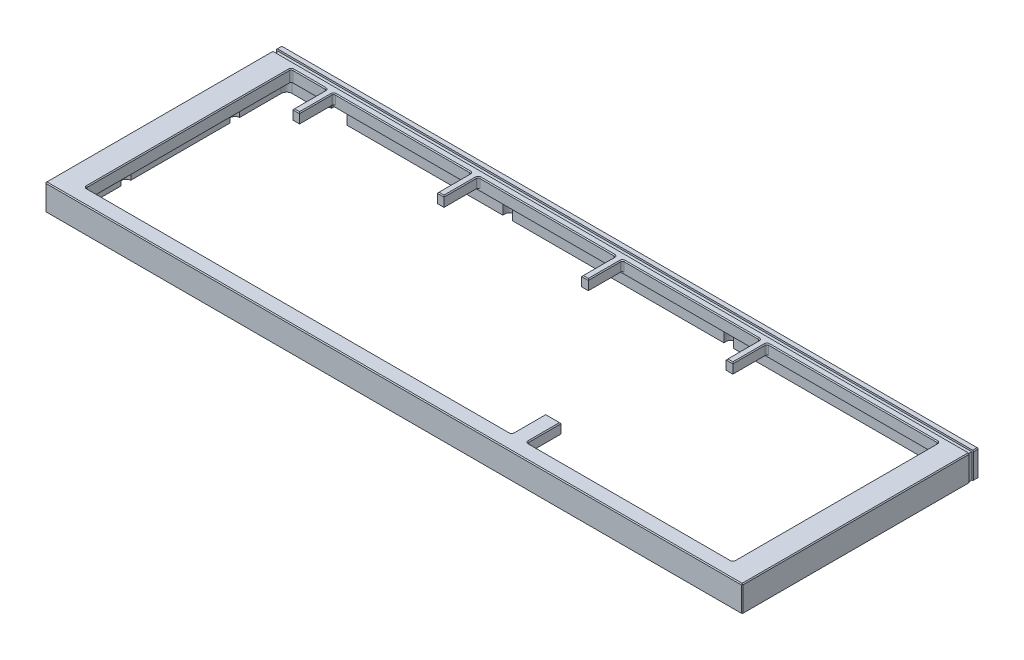
SolidWorks part; units mm, degrees
material "6061-T6 (SS)"
ref_plane "Front Plane" through (0, 0, 0) normal (0, 0, 1) x (1, 0, 0)
ref_plane "Top Plane" through (0, 0, 0) normal (0, 1, 0) x (1, 0, 0)
ref_plane "Right Plane" through (0, 0, 0) normal (1, 0, 0) x (0, 0, -1)
sketch "Sketch1" plane through (0, 0, 0) normal (0, 1, 0) x (1, 0, 0)
  line L1 (0, 0) -> (390.74, 0)
  line L2 (0, 0) -> (0, 132.7)
  line L3 (0, 132.7) -> (390.74, 132.7)
  line L4 (390.74, 0) -> (390.74, 132.7)
  line L5 (13.92, 124) -> (376.82, 124)
  line L6 (13.92, 124) -> (13.92, 8.7)
  line L7 (13.92, 8.7) -> (376.82, 8.7)
  line L8 (376.82, 124) -> (376.82, 8.7)
  point P9 (195.37, 124)
  point P10 (195.37, 132.7)
  point P11 (13.92, 66.35)
  point P12 (0, 66.35)
  dimension "D1" = 362.9
  dimension "D2" = 115.3
  dimension "D3" = 8.7
  dimension "D4" = 13.92
extrude "Main Body" add sketch "Sketch1" along normal blind 14.8
sketch "Sketch2" plane through (0, 0, 0) normal (0, -1, 0) x (1, 0, 0)
  line L0 (390.74, -132.7) -> (0, -132.7) construction
  line L1 (388.74, -130.7) -> (2, -130.7)
  line L2 (388.74, -130.7) -> (388.74, -2)
  line L3 (388.74, -2) -> (2, -2)
  line L4 (2, -130.7) -> (2, -2)
  line L5 (390.74, 0) -> (390.74, -132.7) construction
  point P4 (195.37, -130.7)
  point P7 (195.37, -132.7)
  point P8 (388.74, -66.35)
  point P11 (390.74, -66.35)
  dimension "D1" = 2
  dimension "D2" = 2
extrude "Alignment Guide" cut sketch "Sketch2" against normal blind 1 contours L2 L1 L4 L3
sketch "Sketch3" plane through (0, 14.8, 0) normal (0, 1, 0) x (1, 0, 0)
  line L0 (13.92, 8.7) -> (376.82, 8.7) construction
  line L1 (252.82, 27.8) -> (261.52, 27.8)
  line L2 (252.82, 27.8) -> (252.82, 8.7)
  line L3 (252.82, 8.7) -> (261.52, 8.7)
  line L4 (261.52, 27.8) -> (261.52, 8.7)
  line L5 (376.82, 8.7) -> (376.82, 124) construction
  line L6 (376.82, 124) -> (13.92, 124) construction
  line L7 (33.92, 124) -> (37.72, 124)
  line L8 (33.92, 124) -> (33.92, 104.9)
  line L9 (33.92, 104.9) -> (37.72, 104.9)
  line L10 (37.72, 124) -> (37.72, 104.9)
  line L11 (13.92, 124) -> (13.92, 8.7) construction
  line L12 (114.92, 124) -> (118.72, 124)
  line L13 (114.92, 124) -> (114.92, 104.9)
  line L14 (114.92, 104.9) -> (118.72, 104.9)
  line L15 (118.72, 124) -> (118.72, 104.9)
  line L16 (195.82, 124) -> (199.62, 124)
  line L17 (195.82, 124) -> (195.82, 104.9)
  line L18 (195.82, 104.9) -> (199.62, 104.9)
  line L19 (199.62, 124) -> (199.62, 104.9)
  line L20 (276.82, 124) -> (280.62, 124)
  line L21 (276.82, 124) -> (276.82, 104.9)
  line L22 (276.82, 104.9) -> (280.62, 104.9)
  line L23 (280.62, 124) -> (280.62, 104.9)
  point P8 (257.17, 8.7)
  dimension "D1" = 115.3
  dimension "D2" = 124
  dimension "D3" = 19.1
  dimension "D4" = 3.8
  dimension "D5" = 19.1
  dimension "D6" = 77.2
  dimension "D7" = 77.1
  dimension "D8" = 77.2
  dimension "D9" = 20
extrude "Blockers" add sketch "Sketch3" against normal blind 5.5
fillet "Fillet5" radius 1 14 edges at (280.62, 12.05, -124) (276.82, 12.05, -124) (195.82, 12.05, -124) (199.62, 12.05, -124) (118.72, 12.05, -124) (114.92, 12.05, -124) (33.92, 12.05, -124) (37.72, 12.05, -124) (13.92, 7.9, -124) (13.92, 7.9, -8.7) (252.82, 12.05, -8.7) (261.52, 12.05, -8.7) (376.82, 7.9, -8.7) (376.82, 7.9, -124)
sketch "Sketch4" plane through (0, 1, 0) normal (0, -1, 0) x (1, 0, 0)
  line L0 (0, 0) -> (390.74, 0) construction
  line L1 (381.27, -125.9) -> (9.47, -125.9)
  line L2 (381.27, -125.9) -> (381.27, -6.8)
  line L3 (381.27, -6.8) -> (9.47, -6.8)
  line L4 (9.47, -125.9) -> (9.47, -6.8)
  line L5 (390.74, 0) -> (390.74, -132.7) construction
  point P4 (195.37, -6.8)
  point P7 (195.37, 0)
  point P8 (381.27, -66.35)
  point P11 (390.74, -66.35)
  dimension "D1" = 119.1
  dimension "D2" = 371.8
extrude "PCB Cutout" cut sketch "Sketch4" against normal offset from surface (7.3 mm away) 6.5 up to face at (195.37, 14.8, -66.35)
fillet "Fillet4" radius 3 8 edges at (9.47, 4.65, -6.8) (9.47, 4.65, -125.9) (381.27, 4.65, -125.9) (381.27, 4.65, -6.8) (2, 0.5, -130.7) (2, 0.5, -2) (388.74, 0.5, -2) (388.74, 0.5, -130.7)
sketch "Sketch6" plane through (0, 1, 0) normal (0, -1, 0) x (1, 0, 0)
  line L0 (381.27, -9.8) -> (381.27, -122.9) construction
  line L1 (254.59, -127.1) -> (260.09, -127.1)
  line L2 (254.59, -127.1) -> (254.59, -125.9)
  line L3 (254.59, -125.9) -> (260.09, -125.9)
  line L4 (260.09, -127.1) -> (260.09, -125.9)
  line L5 (12.47, -125.9) -> (378.27, -125.9) construction
  line L11 (378.27, -6.8) -> (12.47, -6.8) construction
  line L16 (260.09, -6.8) -> (254.59, -6.8)
  line L17 (260.09, -6.8) -> (260.09, -4.8)
  line L18 (260.09, -4.8) -> (254.59, -4.8)
  line L19 (254.59, -6.8) -> (254.59, -4.8)
  line L21 (0, 0) -> (390.74, 0) construction
  line L24 (390.74, -66.35) -> (195.37, -66.35) construction
  line L25 (390.74, 0) -> (390.74, -132.7) construction
  line L26 (328.6755, -66.35) -> (328.6755, -130.7) construction
  line L27 (385.74, -130.7) -> (5, -130.7) construction
  line L28 (328.6755, -66.35) -> (328.6755, -8.7) construction
  line L29 (375.82, -8.7) -> (14.92, -8.7) construction
  line L55 (390.74, -132.7) -> (0, -132.7) construction
  line L56 (195.37, -132.7) -> (195.37, 0) construction
  line L57 (136.15, -6.8) -> (136.15, -4.8)
  line L58 (130.65, -4.8) -> (136.15, -4.8)
  line L59 (130.65, -6.8) -> (130.65, -4.8)
  line L60 (130.65, -6.8) -> (136.15, -6.8)
  line L61 (130.65, -127.1) -> (130.65, -125.9)
  line L62 (136.15, -125.9) -> (130.65, -125.9)
  line L63 (136.15, -127.1) -> (136.15, -125.9)
  line L64 (136.15, -127.1) -> (130.65, -127.1)
  circle A0 centre (381.07, -96.85) radius 2.75
  circle A1 centre (381.07, -35.85) radius 2.75
  circle A2 centre (257.34, -4.8) radius 2.75
  circle A3 centre (257.34, -127.1) radius 2.75
  circle A8 centre (133.4, -4.8) radius 2.75
  circle A9 centre (9.67, -35.85) radius 2.75
  circle A10 centre (9.67, -96.85) radius 2.75
  circle A11 centre (133.4, -127.1) radius 2.75
  point P25 (195.37, -66.35)
  point P32 (257.34, -125.9)
  point P33 (257.34, -6.8)
  line M17 (12.47, -6.8) -> (378.27, -6.8)
  line M18 (381.27, -9.8) -> (381.27, -122.9)
  line M19 (378.27, -125.9) -> (12.47, -125.9)
  line M20 (9.47, -122.9) -> (9.47, -9.8)
  dimension "D4" = 5.5
  dimension "D5" = 133.4
  dimension "D1" = 30.5
  dimension "D2" = 4.8
  dimension "D3" = 30.5
  dimension "D6" = 0.2
  dimension "D7" = 5.6
extrude "PlateTabs" cut sketch "Sketch6" against normal up to surface (7.3 mm away) contours A0 M18 | A1 M18 | A2 L19 M17 | L16 A2 L18 | A2 L17 M17 | L18 A2 | L1 A3 | L1 A3 L3 | A3 L2 M19 | A11 L64 | A11 L64 L62 | A10 M20 | A9 M20 | A8 L58 | A8 L60 L58 | A3 L4 M19 | A8 L59 M17 | L57 A8 M17 | A11 L63 M19 | L61 A11 M19 | A11 | L59 L58 L57 L60 | A3 region at (257.34, 1, -126.5102) region at (136.0681, 1, -126.1969) region at (257.34, 1, -128.2671) region at (254.6719, 1, -126.1969) region at (260.0081, 1, -126.1969) region at (133.4, 1, -126.5102) region at (133.4, 1, -128.2671) region at (130.7319, 1, -126.1969) region at (135.9001, 1, -6.317) region at (259.8401, 1, -6.317) region at (257.34, 1, -5.7445) region at (257.34, 1, -3.6329) region at (254.8399, 1, -6.317) region at (133.4, 1, -5.7445) region at (133.4, 1, -3.6329) region at (130.8999, 1, -6.317) region at (382.3459, 1, -96.85) region at (382.3459, 1, -35.85) region at (8.3941, 1, -96.85) region at (8.3941, 1, -35.85) up to face at (195.37, 8.3, -66.35)
sketch "Sketch9" plane through (0, 0, -132.7) normal (0, 0, -1) x (-1, 0, 0)
  line L1 (-41.8, 0) -> (-29.8, 0)
  line L2 (-41.8, 0) -> (-41.8, 3.2)
  line L3 (-41.8, 3.2) -> (-29.8, 3.2)
  line L4 (-29.8, 0) -> (-29.8, 3.2)
  line L5 (-390.74, 0) -> (0, 0) construction
  line L7 (0, 14.8) -> (0, 0) construction
  point P6 (-35.8, 3.2)
  dimension "D1" = 3.2
  dimension "D3" = 12
  dimension "D4" = 35.8
extrude "USB Cutout" cut sketch "Sketch9" against normal up to surface (8.7 mm away) up to face at (164.89, 11.95, -124)
sketch "Sketch11" plane through (0, 0, -125.9) normal (0, 0, 1) x (1, 0, 0)
  line L0 (130.65, 8.3) -> (12.47, 8.3) construction
  line L1 (43.3, 1) -> (28.3, 1)
  line L2 (43.3, 1) -> (43.3, 8.3)
  line L3 (43.3, 8.3) -> (28.3, 8.3)
  line L4 (28.3, 1) -> (28.3, 8.3)
  line L7 (12.47, 1) -> (29.8, 1) construction
  line L8 (29.8, 3.2) -> (41.8, 3.2) construction
  point P8 (35.8, 1)
  point P12 (0, 0)
  point P13 (0, 0)
  point P14 (0, 0)
  point P15 (0, 0)
  point P18 (35.8, 3.2)
  dimension "D1" = 15
extrude "PCB Clearance" cut sketch "Sketch11" against normal blind 3.9
fillet "Fillet7" radius 2.5 2 edges at (28.3, 4.65, -129.8) (43.3, 4.65, -129.8)
sketch "Sketch12" plane through (0, 8.3, 0) normal (0, -1, 0) x (1, 0, 0)
  line L0 (195.37, -132.7) -> (195.37, 0) construction
  line L2 (14.92, -124) -> (375.82, -124) construction
  line L3 (0, 0) -> (390.74, 0) construction
  line L4 (390.74, 0) -> (390.74, -132.7) construction
  line L5 (390.74, -132.7) -> (41.8, -132.7) construction
  line L8 (376.82, -123) -> (376.82, -9.7) construction
  line L9 (375.82, -8.7) -> (14.92, -8.7) construction
  arc A0 (381.27, -38.5927) -> (381.27, -33.1073) centre (381.07, -35.85) ccw construction
  arc A1 (381.27, -99.5927) -> (381.27, -94.1073) centre (381.07, -96.85) ccw construction
  point P0 (257.34, -127.1)
  point P1 (381.42, -96.85)
  point P2 (381.42, -35.85)
  point P3 (257.34, -4.8)
  point P7 (195.37, -131.4428)
  point P8 (133.4, -4.8)
  point P10 (9.32, -35.85)
  point P12 (0, 0)
  point P14 (9.32, -96.85)
  point P16 (133.4, -127.1)
  point P34 (383.82, -35.85)
  point P39 (383.82, -96.85)
  dimension "D1" = 3.1
  dimension "D2" = 3.9
  dimension "D3" = 4.6
  dimension "D4" = 133.4
sketch "Sketch14" plane through (0, 1, 0) normal (0, -1, 0) x (1, 0, 0)
  line L0 (195.37, -132.7) -> (195.37, 0) construction
  line L2 (0, 0) -> (390.74, 0) construction
  line L3 (390.74, -132.7) -> (41.8, -132.7) construction
  line L5 (195.37, -66.35) -> (390.74, -66.35) construction
  line L6 (390.74, 0) -> (390.74, -132.7) construction
  line L7 (388.74, -127.7) -> (388.74, -5) construction
  line L8 (385.74, -130.7) -> (41.8, -130.7) construction
  line L9 (385.74, -2) -> (5, -2) construction
  point P2 (0, 0)
  point P8 (385.04, -111.35)
  point P9 (385.04, -66.35)
  point P10 (385.04, -21.35)
  point P11 (280.74, -4.4)
  point P20 (280.74, -128.3)
  point P22 (110, -4.4)
  point P28 (110, -128.3)
  point P29 (5.7, -21.35)
  point P30 (5.7, -66.35)
  point P31 (5.7, -111.35)
  dimension "D1" = 2.4
  dimension "D2" = 2.4
  dimension "D3" = 110
  dimension "D4" = 45
  dimension "D5" = 45
  dimension "D6" = 3.7
chamfer "Chamfer1" distance 0.5 42 edges at (14.2129, 14.8, -8.9929) (133.37, 14.8, -8.7) (252.5271, 14.8, -8.9929) (252.82, 14.8, -18.75) (257.17, 14.8, -27.8) (261.52, 14.8, -18.75) (261.8129, 14.8, -8.9929) (319.17, 14.8, -8.7) (376.5271, 14.8, -8.9929) (376.82, 14.8, -66.35) (376.5271, 14.8, -123.7071) (328.72, 14.8, -124) (280.9129, 14.8, -123.7071) (280.62, 14.8, -113.95) (278.72, 14.8, -104.9) (276.82, 14.8, -113.95) (276.5271, 14.8, -123.7071) (238.22, 14.8, -124) (199.9129, 14.8, -123.7071) (199.62, 14.8, -113.95) (197.72, 14.8, -104.9) (195.82, 14.8, -113.95) (195.5271, 14.8, -123.7071) (157.27, 14.8, -124) (119.0129, 14.8, -123.7071) (118.72, 14.8, -113.95) (116.82, 14.8, -104.9) (114.92, 14.8, -113.95) (114.6271, 14.8, -123.7071) (76.32, 14.8, -124) (38.0129, 14.8, -123.7071) (37.72, 14.8, -113.95) (35.82, 14.8, -104.9) (33.92, 14.8, -113.95) (33.6271, 14.8, -123.7071) (23.92, 14.8, -124) (14.2129, 14.8, -123.7071) (13.92, 14.8, -66.35) (195.37, 14.8, -132.7) (390.74, 14.8, -66.35) (195.37, 14.8, 0) (0, 14.8, -66.35)
chamfer "Chamfer2" distance 0.5 9 edges at (0, 7.15, -132.7) (216.27, 0, -132.7) (14.9, 0, -132.7) (390.74, 7.15, -132.7) (390.74, 0, -66.35) (390.74, 7.15, 0) (0, 7.15, 0) (195.37, 0, 0) (0, 0, -66.35)
sketch "Sketch27" plane through (0, 14.8, 0) normal (0, 1, 0) x (1, 0, 0)
  line L0 (0, 0.5) -> (0, 132.2) construction
  line L1 (0, 129.7) -> (390.74, 129.7)
  line L2 (0, 129.7) -> (0, 127.2)
  line L3 (0, 127.2) -> (390.74, 127.2)
  line L4 (390.74, 129.7) -> (390.74, 127.2)
  line L5 (390.74, 132.2) -> (390.74, 0.5) construction
  line L8 (0.5, 132.7) -> (390.24, 132.7) construction
  dimension "D1" = 2.5
  dimension "D2" = 3
extrude "Cut-Extrude11" cut sketch "Sketch27" against normal blind 1
sketch "Sketch28" plane through (0, 13.8, 0) normal (0, 1, 0) x (1, 0, 0)
  line L1 (0, 129.7) -> (1, 129.7)
  line L2 (0, 129.7) -> (0, 127.2)
  line L3 (0, 127.2) -> (1, 127.2)
  line L4 (1, 129.7) -> (1, 127.2)
  line L5 (389.74, 129.7) -> (390.74, 129.7)
  line L6 (389.74, 129.7) -> (389.74, 127.2)
  line L7 (389.74, 127.2) -> (390.74, 127.2)
  line L8 (390.74, 129.7) -> (390.74, 127.2)
  line L9 (390.74, 129.7) -> (0, 129.7) construction
  line L10 (0, 127.2) -> (390.74, 127.2) construction
  dimension "D1" = 1
  dimension "D2" = 1
extrude "Cut-Extrude12" cut sketch "Sketch28" against normal through all
sketch "Sketch21" [suppressed] plane through (0, 14.8, 0) normal (0, 1, 0) x (1, 0, 0)
  line L0 (0.5, 132.7) -> (390.24, 132.7) construction
  line L1 (382.53, 132.7) -> (385.03, 132.7)
  line L2 (382.53, 132.7) -> (382.53, 72.7)
  line L3 (382.53, 72.7) -> (385.03, 72.7)
  line L4 (385.03, 132.7) -> (385.03, 72.7)
  line L5 (390.74, 132.2) -> (390.74, 129.7) construction
  line L6 (390.74, 129.1) -> (294.74, 129.1)
  line L7 (390.74, 129.1) -> (390.74, 127.6)
  line L8 (390.74, 127.6) -> (294.74, 127.6)
  line L9 (294.74, 129.1) -> (294.74, 127.6)
  line L10 (362.9081, 132.2) -> (362.9081, 124.5) construction
  line L11 (390.24, 132.2) -> (0.5, 132.2) construction
  line L12 (281.62, 124.5) -> (375.82, 124.5) construction
  line L13 (365.5702, 129.1) -> (365.5702, 127.6) construction
  line L14 (377.32, 119.5259) -> (390.24, 119.5259) construction
  line L15 (377.32, 123) -> (377.32, 9.7) construction
  line L16 (390.24, 0.5) -> (390.24, 127.2) construction
  line L17 (382.53, 116.0504) -> (385.03, 116.0504) construction
  point P28 (383.78, 116.0504)
  point P29 (383.78, 119.5259)
  point P30 (365.5702, 128.35)
  point P31 (362.9081, 128.35)
  dimension "D1" = 2.5
  dimension "D2" = 1.5
  dimension "D3" = 60
  dimension "D4" = 96
extrude "Cut-Extrude5" [suppressed] cut sketch "Sketch21" against normal blind 1 contours L4 L3 L2 L1 | L8 L9 L6 L7
sketch "Sketch23" [suppressed] plane through (390.74, 0, 0) normal (1, 0, 0) x (0, 0, -1)
  line L0 (129.1, 13.8) -> (129.1, 14.3) construction
  line L1 (127.6, 13.8) -> (129.1, 13.8)
  line L2 (127.6, 13.8) -> (127.6, 0)
  line L3 (127.6, 0) -> (129.1, 0)
  line L4 (129.1, 13.8) -> (129.1, 0)
extrude "Cut-Extrude6" [suppressed] cut sketch "Sketch23" against normal blind 1
sketch "Sketch20" plane through (0, 14.8, 0) normal (0, 1, 0) x (1, 0, 0)
  line L0 (0, 0.5) -> (0, 127.2) construction
  line L1 (0, 129.1) -> (390.74, 129.1)
  line L2 (0, 129.1) -> (0, 127.6)
  line L3 (0, 127.6) -> (390.74, 127.6)
  line L4 (390.74, 129.1) -> (390.74, 127.6)
  line L5 (390.74, 132.2) -> (390.74, 129.7) construction
  line L6 (0.5, 132.7) -> (390.24, 132.7) construction
  line L7 (381.7523, 132.7) -> (384.2523, 132.7)
  line L8 (381.7523, 132.7) -> (381.7523, 0)
  line L9 (381.7523, 0) -> (384.2523, 0)
  line L10 (384.2523, 132.7) -> (384.2523, 0)
  line L11 (390.24, 0) -> (0.5, 0) construction
  line L12 (376.82, 111.1489) -> (390.74, 111.1489) construction
  line L13 (376.82, 9.7) -> (376.82, 123) construction
  line L14 (381.7523, 114.604) -> (384.2523, 114.604) construction
  line L15 (369.2566, 124.5) -> (369.2566, 132.2) construction
  line L16 (281.62, 124.5) -> (375.82, 124.5) construction
  line L17 (390.24, 132.2) -> (0.5, 132.2) construction
  line L18 (371.0168, 127.6) -> (371.0168, 129.1) construction
  point P30 (371.0168, 128.35)
  point P31 (369.2566, 128.35)
  dimension "D1" = 2.5
  dimension "D2" = 1.5
extrude "Cut-Extrude4" [suppressed] cut sketch "Sketch20" against normal blind 1
sketch "Sketch19" plane through (0, 14.8, 0) normal (0, 1, 0) x (1, 0, 0)
  line L0 (0.5, 132.7) -> (390.24, 132.7) construction
  line L1 (5.46, 132.7) -> (8.46, 132.7)
  line L2 (5.46, 132.7) -> (5.46, 0)
  line L3 (5.46, 0) -> (8.46, 0)
  line L4 (8.46, 132.7) -> (8.46, 0)
  line L7 (382.28, 132.7) -> (385.28, 132.7)
  line L8 (382.28, 132.7) -> (382.28, 0)
  line L9 (382.28, 0) -> (385.28, 0)
  line L10 (385.28, 132.7) -> (385.28, 0)
  line L11 (390.24, 0) -> (0.5, 0) construction
  line L12 (377.32, 110.209) -> (390.24, 110.209) construction
  line L13 (377.32, 123) -> (377.32, 9.7) construction
  line L14 (390.24, 0.5) -> (390.24, 127.2) construction
  line L15 (382.28, 106.8719) -> (385.28, 106.8719) construction
  line L16 (0.5, 106.8719) -> (13.42, 106.8719) construction
  line L17 (0.5, 132.2) -> (0.5, 129.7) construction
  line L18 (13.42, 9.7) -> (13.42, 123) construction
  line L19 (5.46, 102.7297) -> (8.46, 102.7297) construction
  point P12 (383.78, 106.8719)
  point P14 (383.78, 110.209)
  point P30 (6.96, 102.7297)
  point P31 (6.96, 106.8719)
  dimension "D1" = 3
  dimension "D2" = 3
extrude "Cut-Extrude3" [suppressed] cut sketch "Sketch19" against normal blind 1
sketch "Sketch17" plane through (0, 14.8, 0) normal (0, 1, 0) x (1, 0, 0)
  line L0 (390.24, 0.5) -> (390.24, 127.2) construction
  line L1 (5.71, 129.6) -> (385.03, 129.6)
  line L2 (5.71, 129.6) -> (5.71, -1.9)
  line L3 (5.71, -1.9) -> (385.03, -1.9)
  line L4 (385.03, 129.6) -> (385.03, -1.9)
  line L5 (8.21, 127.1) -> (382.53, 127.1)
  line L6 (8.21, 127.1) -> (8.21, 0.6)
  line L7 (8.21, 0.6) -> (382.53, 0.6)
  line L8 (382.53, 127.1) -> (382.53, 0.6)
  line L9 (390.24, 132.2) -> (0.5, 132.2) construction
  line L10 (21.2533, 132.2) -> (21.2533, 124.5) construction
  line L11 (14.92, 124.5) -> (32.92, 124.5) construction
  line L12 (25.2757, 129.6) -> (25.2757, 127.1) construction
  line L13 (0.5, 116.1326) -> (13.42, 116.1326) construction
  line L14 (0.5, 132.2) -> (0.5, 129.7) construction
  line L15 (13.42, 9.7) -> (13.42, 123) construction
  line L16 (5.71, 120.1548) -> (8.21, 120.1548) construction
  point P8 (382.53, 63.85)
  point P9 (385.03, 63.85)
  point P12 (390.24, 63.85)
  point P13 (195.37, 129.6)
  point P14 (195.37, 127.1)
  point P17 (195.37, 132.2)
  point P24 (25.2757, 128.35)
  point P25 (21.2533, 128.35)
  point P34 (6.96, 116.1326)
  point P35 (6.96, 120.1548)
  dimension "D1" = 2.5
  dimension "D2" = 2.5
extrude "Cut-Extrude1" [suppressed] cut sketch "Sketch17" against normal blind 1
hole_wizard "M3x0.5 Tapped Hole1" positions "3DSketch1" profile "Sketch29" tap size "M3x0.5" standard "ANSI Metric"
sketch3d "3DSketch1"
  point P0 (385.04, 1, -111.35)
  point P3 (385.04, 1, -21.35)
  point P6 (280.74, 1, -4.4)
  point P9 (110, 1, -4.4)
  point P12 (5.7, 1, -21.35)
  point P15 (5.7, 1, -66.35)
  point P18 (5.7, 1, -111.35)
  point P21 (110, 1, -128.3)
  point P24 (280.74, 1, -128.3)
  point P28 (385.04, 1, -66.35)
sketch "Sketch29" plane through (385.04, 1, -111.35) normal (1, 0, 0) x (0, 0, -1)
  line L0 (0, 0) -> (0, 4.7511)
  line L1 (0, 4.7511) -> (1.25, 4)
  line L2 (1.25, 4) -> (1.25, 0)
  line L5 (1.25, 0) -> (0, 0)
  line L10 (0, 4.7511) -> (-1.25, 4) construction
  line L11 (0, -6.35) -> (0, 107.95) construction
  dimension "Tap Drill Dia." = 2.5
  dimension "Tap Drill Depth" = 4
  dimension "Drill Angle" = 118
cosmetic thread "Hole Thread1" parameters "D1"=4, "D2"=3
cosmetic thread "Hole Thread2" parameters "D1"=4, "D2"=3
cosmetic thread "Hole Thread3" parameters "D1"=4, "D2"=3
cosmetic thread "Hole Thread4" parameters "D1"=4, "D2"=3
cosmetic thread "Hole Thread5" parameters "D1"=4, "D2"=3
cosmetic thread "Hole Thread6" parameters "D1"=4, "D2"=3
cosmetic thread "Hole Thread7" parameters "D1"=4, "D2"=3
cosmetic thread "Hole Thread8" parameters "D1"=4, "D2"=3
cosmetic thread "Hole Thread9" parameters "D1"=4, "D2"=3
cosmetic thread "Hole Thread18" parameters "D1"=4, "D2"=3
hole_wizard "M2x0.4 Tapped Hole1" positions "3DSketch3" profile "Sketch31" tap size "M2x0.4" standard "ANSI Metric"
sketch3d "3DSketch3"
  point P0 (381.42, 8.3, -96.85)
  point P3 (381.42, 8.3, -35.85)
  point P7 (257.34, 8.3, -4.8)
  point P10 (133.4, 8.3, -4.8)
  point P13 (9.32, 8.3, -35.85)
  point P16 (9.32, 8.3, -96.85)
  point P19 (133.4, 8.3, -127.1)
  point P22 (257.34, 8.3, -127.1)
sketch "Sketch31" plane through (381.42, 8.3, -96.85) normal (1, 0, 0) x (0, 0, -1)
  line L0 (0, 0) -> (0, 4.4807)
  line L1 (0, 4.4807) -> (0.8, 4)
  line L2 (0.8, 4) -> (0.8, 0)
  line L5 (0.8, 0) -> (0, 0)
  line L10 (0, 4.4807) -> (-0.8, 4) construction
  line L11 (0, -6.35) -> (0, 107.95) construction
  dimension "Tap Drill Dia." = 1.6
  dimension "Tap Drill Depth" = 4
  dimension "Drill Angle" = 118
cosmetic thread "Hole Thread19" parameters "D1"=4, "D2"=2
cosmetic thread "Hole Thread20" parameters "D1"=4, "D2"=2
cosmetic thread "Hole Thread21" parameters "D1"=4, "D2"=2
cosmetic thread "Hole Thread22" parameters "D1"=4, "D2"=2
cosmetic thread "Hole Thread23" parameters "D1"=4, "D2"=2
cosmetic thread "Hole Thread24" parameters "D1"=4, "D2"=2
cosmetic thread "Hole Thread25" parameters "D1"=4, "D2"=2
cosmetic thread "Hole Thread26" parameters "D1"=4, "D2"=2
fillet "Fillet8" radius 0.1 9 edges at (213.77, 0, -130.7) (387.8613, 0, -129.8213) (17.4, 0, -130.7) (2.8787, 0, -129.8213) (2, 0, -66.35) (2.8787, 0, -2.8787) (195.37, 0, -2) (387.8613, 0, -2.8787) (388.74, 0, -66.35)
